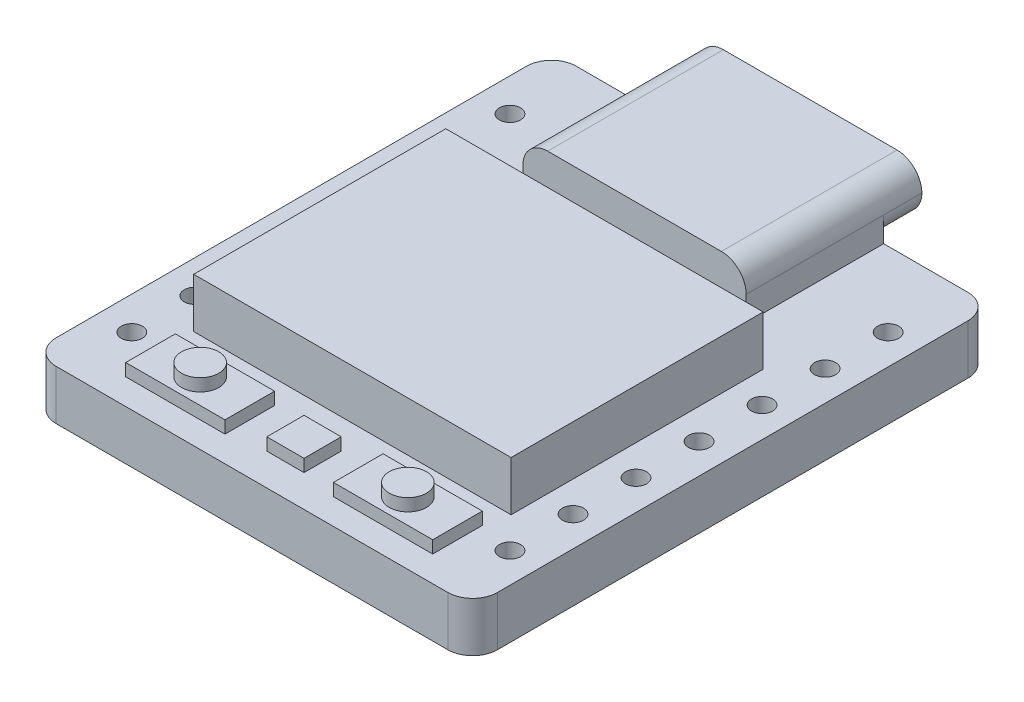
SolidWorks part; units mm, degrees
ref_plane "Plan de face" through (0, 0, 0) normal (0, 0, 1) x (1, 0, 0)
ref_plane "Plan de dessus" through (0, 0, 0) normal (0, 1, 0) x (1, 0, 0)
ref_plane "Plan de droite" through (0, 0, 0) normal (1, 0, 0) x (0, 0, -1)
sketch "Esquisse1" plane through (0, 0, 0) normal (0, 1, 0) x (1, 0, 0)
  line L0 (-8.89, 7.4775) -> (-7.56, 7.4775) construction
  line L1 (-8.89, -10.4775) -> (8.89, -10.4775)
  line L2 (-8.89, -10.4775) -> (-8.89, 10.4775)
  line L3 (-8.89, 10.4775) -> (8.89, 10.4775)
  line L4 (8.89, -10.4775) -> (8.89, 10.4775)
  line L5 (-8.89, -10.4775) -> (8.89, 10.4775) construction
  line L6 (-8.89, 10.4775) -> (8.89, -10.4775) construction
  line L7 (-7.56, 7.4775) -> (-7.56, 10.4775) construction
  circle A0 centre (-7.56, 7.4775) radius 0.425
  circle A1 centre (7.68, 7.4775) radius 0.425
  circle A2 centre (7.68, 4.9375) radius 0.425
  circle A3 centre (7.68, 2.3975) radius 0.425
  circle A4 centre (7.68, -0.1425) radius 0.425
  circle A5 centre (7.68, -2.6825) radius 0.425
  circle A6 centre (7.68, -5.2225) radius 0.425
  circle A7 centre (7.68, -7.7625) radius 0.425
  circle A8 centre (-7.56, 4.9375) radius 0.425
  circle A9 centre (-7.56, 2.3975) radius 0.425
  circle A10 centre (-7.56, -0.1425) radius 0.425
  circle A11 centre (-7.56, -2.6825) radius 0.425
  circle A12 centre (-7.56, -5.2225) radius 0.425
  circle A13 centre (-7.56, -7.7625) radius 0.425
  point P0 (0, 0)
  dimension "D5" = 0.85
  dimension "D1" = 17.78
  dimension "D2" = 20.955
  dimension "D3" = 1.33
  dimension "D4" = 3
  dimension "D6" = 2
  dimension "D7" = 7
extrude "Boss.-Extru.1" add sketch "Esquisse1" along normal blind 2
sketch "Esquisse2" plane through (0, 2, 0) normal (0, 1, 0) x (1, 0, 0)
  line L0 (-7.56, 7.4775) -> (7.68, 7.4775) construction
  line L1 (0, 12.0175) -> (0, 10.4775) construction
  line L2 (-4.5, 12.0175) -> (4.5, 12.0175)
  line L3 (-4.5, 12.0175) -> (-4.5, 7.4775)
  line L4 (4.5, 12.0175) -> (4.5, 7.4775)
  line L6 (8.89, 10.4775) -> (-8.89, 10.4775) construction
  line L7 (-7.56, 4.9375) -> (7.68, 4.9375) construction
  line L8 (-4.5, 7.4775) -> (-4.5, 4.9375)
  line L9 (-4.5, 4.9375) -> (4.5, 4.9375)
  line L10 (4.5, 4.9375) -> (4.5, 7.4775)
  point P8 (0, 12.0175)
  dimension "D1" = 1.54
  dimension "D2" = 9
extrude "Boss.-Extru.2" add sketch "Esquisse2" along normal blind 2
fillet "Congé1" radius 1 4 edges at (-4.5, 2, -11.2475) (4.5, 2, -11.2475) (-4.5, 4, -8.4775) (4.5, 4, -8.4775)
sketch "Esquisse3" plane through (0, 0, -12.0175) normal (0, 0, -1) x (-1, 0, 0)
  line L0 (0, 2) -> (0, 4) construction
  line L1 (-3.5, 2) -> (3.5, 2) construction
  line L2 (-3.5, 4) -> (3.5, 4) construction
  line L3 (-3.2497, 3.075) -> (-3.2497, 3.5) construction
  line L4 (-3.2497, 2.5) -> (3.2497, 2.5)
  line L5 (-3.7082, 2.9585) -> (-3.7082, 3.075)
  line L6 (-3.2497, 3.5) -> (3.2497, 3.5)
  line L7 (3.7082, 2.9585) -> (3.7082, 3.0415)
  line L8 (-3.7082, 2.5) -> (3.7082, 3.5) construction
  line L9 (-3.7082, 3.5) -> (3.7082, 2.5) construction
  line L10 (-3.2497, 2.925) -> (3.2497, 2.925)
  line L11 (-3.2497, 2.925) -> (-3.2497, 3.075)
  line L12 (-3.2497, 3.075) -> (3.2497, 3.075)
  line L13 (3.2497, 2.925) -> (3.2497, 3.075)
  line L14 (-3.2497, 2.925) -> (3.2497, 3.075) construction
  line L15 (-3.2497, 3.075) -> (3.2497, 2.925) construction
  line L16 (-3.2497, 3.075) -> (-3.7082, 3.075) construction
  line L17 (-3.2497, 3) -> (-3.4823, 3) construction
  line L18 (-3.4823, 3) -> (-3.7082, 3) construction
  arc A0 (-3.2497, 3.5) -> (-3.7082, 3) centre (-3.2289, 3.0207) ccw
  arc A1 (3.2497, 3.5) -> (3.7082, 3) centre (3.2289, 3.0207) cw
  arc A2 (3.2497, 2.5) -> (3.7082, 3) centre (3.2289, 2.9793) ccw
  arc A3 (-3.2497, 2.5) -> (-3.7082, 3) centre (-3.2289, 2.9793) cw
  point P6 (0, 3)
  point P11 (0, 3)
extrude "Enlèv. mat.-Extru.1" cut sketch "Esquisse3" against normal blind 4 contours A3 L4 A2 L7 A1 L6 A0 L5 L13 L10 L11 L12 region at (3.5152, 2.693, -12.0175)
fillet "Congé2" radius 1 4 edges at (8.89, 1, 10.4775) (-8.89, 1, 10.4775) (-8.89, 1, -10.4775) (8.89, 1, -10.4775)
sketch "Esquisse4" plane through (0, 2, 0) normal (0, 1, 0) x (1, 0, 0)
  line L0 (-7.56, 2.3975) -> (-7.56, 4.9375) construction
  line L1 (7.68, 4.9375) -> (7.68, 2.3975) construction
  line L2 (-7.56, 3.6675) -> (7.68, 3.6675) construction
  line L3 (-7.56, -7.7625) -> (-7.56, -10.4775) construction
  line L4 (-7.89, -10.4775) -> (7.89, -10.4775) construction
  line L5 (7.68, -7.7625) -> (7.68, -10.4775) construction
  line L6 (-7.56, -9.12) -> (7.68, -9.12) construction
  line L7 (-6.335, 2.5788) -> (6.455, 2.5788) construction
  line L8 (0.06, 3.6675) -> (0.06, 2.5788) construction
  line L9 (-6.335, 3.6675) -> (-6.335, -6.4925)
  line L11 (6.455, -6.4925) -> (6.455, 3.6675)
  line L12 (6.455, 3.6675) -> (-6.335, 3.6675)
  line L13 (-7.56, -7.7625) -> (-7.56, -5.2225) construction
  line L14 (-7.56, -6.4925) -> (7.68, -6.4925) construction
  line L15 (-6.335, -6.4925) -> (6.455, -6.4925)
  line L16 (-7.56, -7.7625) -> (7.68, -7.7625) construction
  line L17 (0.06, 2.5788) -> (0.06, -10.4775) construction
  line L18 (-0.69, -8.37) -> (-7.56, -8.37) construction
  line L23 (-0.69, -9.87) -> (0.81, -8.37) construction
  line L24 (-0.69, -8.37) -> (0.81, -9.87) construction
  line L25 (-4.125, -8.37) -> (-4.125, -9.12) construction
  line L31 (-2.125, -8.12) -> (-6.125, -10.12) construction
  line L32 (-2.125, -10.12) -> (-6.125, -8.12) construction
  point P23 (0.06, 2.5788)
  point P26 (0.06, -9.12)
  dimension "D1" = 12.79
  dimension "D2" = 1.5
  dimension "D3" = 1.5
  dimension "D4" = 2
  dimension "D5" = 4
extrude "Boss.-Extru.3" add sketch "Esquisse4" along normal blind 2 contours L9 L15 L11 L12
sketch "Esquisse5" plane through (0, 2, 0) normal (0, 1, 0) x (1, 0, 0)
  line L0 (-7.56, -7.7625) -> (7.68, -7.7625) construction
  line L1 (7.68, -7.7625) -> (7.68, -10.4775) construction
  line L2 (-7.89, -10.4775) -> (7.89, -10.4775) construction
  line L3 (7.68, -10.4775) -> (-7.56, -10.4775) construction
  line L4 (-7.56, -10.4775) -> (-7.56, -7.7625) construction
  line L5 (0.06, -7.7625) -> (0.06, -10.4775) construction
  line L6 (-0.69, -9.12) -> (-7.56, -9.12) construction
  line L11 (-0.69, -9.87) -> (0.81, -8.37) construction
  line L12 (-0.69, -8.37) -> (0.81, -9.87) construction
  line L13 (0.81, -9.12) -> (7.68, -9.12) construction
  line L14 (-4.125, -9.12) -> (-4.125, -7.7625) construction
  line L19 (-2.125, -10.07) -> (-6.125, -8.17) construction
  line L20 (-2.125, -8.17) -> (-6.125, -10.07) construction
  line L21 (-4.125, -8.4413) -> (0.06, -8.4413) construction
  line L22 (-6.125, -9.4413) -> (-2.125, -9.4413)
  line L23 (-6.125, -9.4413) -> (-6.125, -7.4413)
  line L24 (-6.125, -7.4413) -> (-2.125, -7.4413)
  line L25 (-2.125, -9.4413) -> (-2.125, -7.4413)
  line L26 (-6.125, -9.4413) -> (-2.125, -7.4413) construction
  line L27 (-6.125, -7.4413) -> (-2.125, -9.4413) construction
  line L28 (6.245, -7.4413) -> (2.245, -7.4413)
  line L29 (-0.69, -9.1913) -> (0.81, -9.1913)
  line L30 (-0.69, -9.1913) -> (-0.69, -7.6913)
  line L31 (-0.69, -7.6913) -> (0.81, -7.6913)
  line L32 (0.81, -9.1913) -> (0.81, -7.6913)
  line L33 (-0.69, -9.1913) -> (0.81, -7.6913) construction
  line L34 (-0.69, -7.6913) -> (0.81, -9.1913) construction
  line L35 (2.245, -9.4413) -> (2.245, -7.4413)
  line L36 (6.245, -9.4413) -> (2.245, -9.4413)
  line L37 (6.245, -9.4413) -> (6.245, -7.4413)
  point P10 (0.06, -9.12)
  point P19 (-4.125, -9.12)
  point P26 (-4.125, -8.4413)
  dimension "D1" = 1.5
  dimension "D2" = 1.5
  dimension "D3" = 4
  dimension "D4" = 1.9
  dimension "D5" = 2
  dimension "D6" = 1.5
  dimension "D7" = 1.5
extrude "Boss.-Extru.4" add sketch "Esquisse5" along normal blind 0.5
sketch "Esquisse6" plane through (0, 2.5, 0) normal (0, 1, 0) x (1, 0, 0)
  line L0 (-2.125, -7.4413) -> (-6.125, -9.4413) construction
  line L1 (0.06, -7.6913) -> (0.06, -9.1913) construction
  line L2 (0.81, -7.6913) -> (-0.69, -7.6913) construction
  line L3 (-0.69, -9.1913) -> (0.81, -9.1913) construction
  circle A0 centre (-4.125, -8.4413) radius 0.75
  circle A1 centre (4.245, -8.4413) radius 0.75
  dimension "D1" = 1.5
extrude "Boss.-Extru.5" add sketch "Esquisse6" along normal blind 0.5
